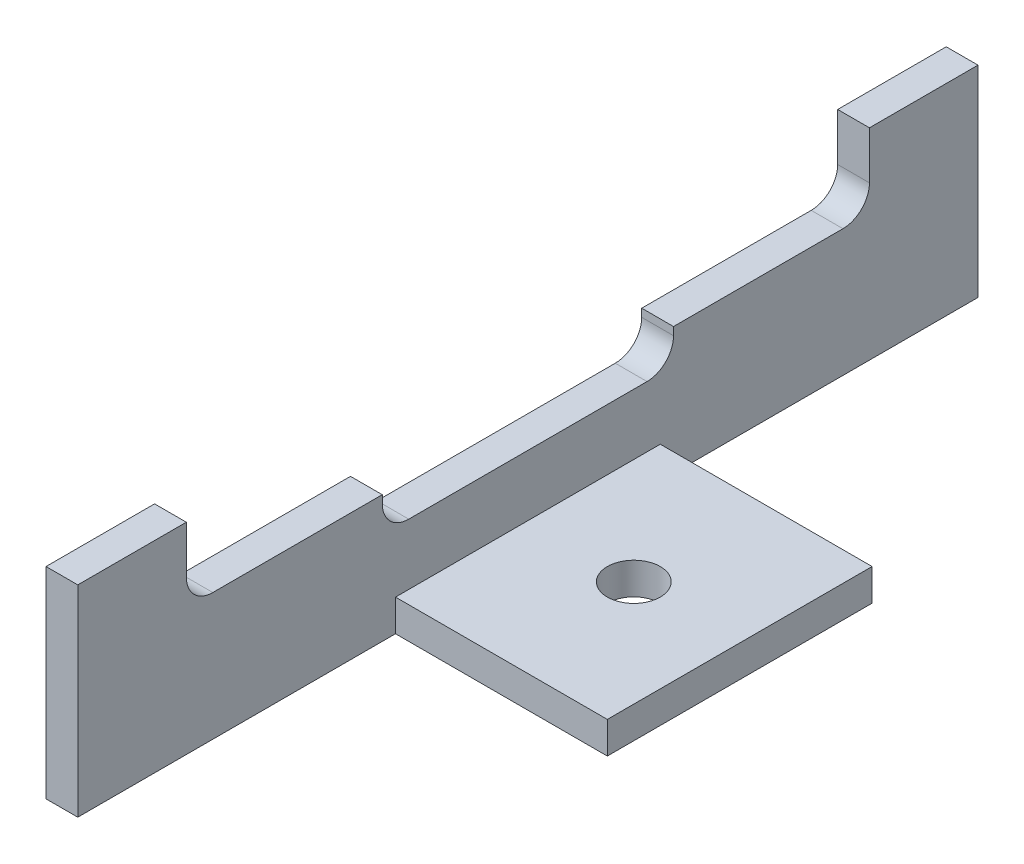
SolidWorks part; units mm, degrees
ref_plane "Alzado" through (0, 0, 0) normal (0, 0, 1) x (1, 0, 0)
ref_plane "Planta" through (0, 0, 0) normal (0, 1, 0) x (1, 0, 0)
ref_plane "Vista lateral" through (0, 0, 0) normal (1, 0, 0) x (0, 0, -1)
sketch "Croquis1" plane through (0, 0, 0) normal (0, 0, 1) x (1, 0, 0)
  line L0 (0, 0) -> (0, 50)
  line L1 (0, 0) -> (50, 0)
  line L2 (6, 6) -> (50, 6)
  line L3 (6, 6) -> (6, 50)
  line L4 (0, 50) -> (6, 50)
  line L5 (50, 6) -> (50, 0)
  dimension "D2" = 50
  dimension "D1" = 6
extrude "Saliente-Extruir1" add sketch "Croquis1" along normal blind 170
sketch "Croquis2" plane through (0, 0, 0) normal (-1, 0, 0) x (0, 0, 1)
  line L0 (170, 35) -> (0, 35) construction
  line L1 (170, 50) -> (170, 0) construction
  line L2 (0, 50) -> (0, 0) construction
  line L3 (170, 6) -> (0, 6) construction
  line L4 (170, 6) -> (0, 6) construction
  line L5 (85, 6) -> (85, 50) construction
  line L6 (170, 50) -> (0, 50) construction
  line L7 (112.5, 17.5) -> (112.5, 50)
  line L8 (112.5, 82.5) -> (57.5, 82.5) construction
  line L9 (112.5, 82.5) -> (112.5, 17.5) construction
  line L10 (112.5, 17.5) -> (57.5, 17.5)
  line L11 (57.5, 82.5) -> (57.5, 17.5) construction
  line L12 (112.5, 82.5) -> (57.5, 17.5) construction
  line L13 (112.5, 17.5) -> (57.5, 82.5) construction
  line L14 (57.5, 17.5) -> (57.5, 50)
  line L15 (57.5, 50) -> (112.5, 50)
  line L16 (149.5, 35) -> (149.5, 50)
  line L17 (130.5, 35) -> (130.5, 50)
  line L18 (130.5, 50) -> (149.5, 50)
  line L19 (39.5, 35) -> (39.5, 50)
  line L20 (20.5, 35) -> (20.5, 50)
  line L21 (39.5, 50) -> (20.5, 50)
  line L22 (170, 0) -> (0, 0) construction
  circle A0 centre (140, 35) radius 9.5 construction
  circle A1 centre (30, 35) radius 9.5 construction
  arc A2 (149.5, 35) -> (130.5, 35) centre (140, 35) cw
  arc A3 (39.5, 35) -> (20.5, 35) centre (30, 35) cw
  dimension "D2" = 19
  dimension "D1" = 35
  dimension "D3" = 55
  dimension "D4" = 55
  dimension "D5" = 17.5
  dimension "D6" = 55
  dimension "D7" = 20.5
  dimension "D8" = 20.5
extrude "Cortar-Extruir1" cut sketch "Croquis2" against normal up to surface (6 mm away) up to face at (6, 28, 85)
sketch "Croquis3" plane through (0, 0, 0) normal (0, -1, 0) x (1, 0, 0)
  line L0 (0, 85) -> (50, 85) construction
  line L1 (0, 170) -> (0, 0) construction
  line L2 (50, 170) -> (50, 0) construction
  line L3 (6, 170) -> (6, 0) construction
  line L4 (50, 0) -> (6, 0)
  line L5 (50, 0) -> (50, 60)
  line L6 (50, 60) -> (6, 60)
  line L7 (6, 0) -> (6, 60)
  line L8 (6, 170) -> (6, 0) construction
  line L9 (50, 110) -> (6, 110)
  line L10 (6, 170) -> (6, 110)
  line L11 (50, 170) -> (6, 170)
  line L12 (50, 170) -> (50, 110)
  line M5 (0, 0) -> (50, 0)
  line M6 (50, 0) -> (50, 170)
  line M7 (50, 170) -> (0, 170)
  dimension "D1" = 60
extrude "Cortar-Extruir2" cut sketch "Croquis3" against normal up to surface (6 mm away) contours L10 L9 M7 M6 | L7 L6 M5 M6 region at (28, 0, 140) region at (28, 0, 30) up to face at (28, 6, 85)
sketch "Croquis4" plane through (0, 0, 0) normal (0, -1, 0) x (1, 0, 0)
  line L0 (46, 60) -> (46, 110)
  line L1 (50, 60) -> (6, 60) construction
  line L2 (50, 110) -> (6, 110) construction
  line L3 (46, 110) -> (50, 110)
  line L4 (50, 110) -> (50, 60)
  line L5 (50, 60) -> (46, 60)
  dimension "D1" = 4
extrude "Cortar-Extruir3" cut sketch "Croquis4" against normal blind 10
sketch "Croquis5" plane through (0, 0, 0) normal (-1, 0, 0) x (0, 0, 1)
  line L0 (170, 38) -> (0, 38) construction
  line L1 (170, 50) -> (170, 0) construction
  line L2 (0, 50) -> (0, 0) construction
  line L3 (170, 50) -> (149.5, 50) construction
  line L4 (170, 38) -> (149.5, 38)
  line L5 (149.5, 38) -> (149.5, 50)
  line L6 (149.5, 50) -> (170, 50)
  line L7 (170, 50) -> (170, 38)
  line L8 (149.5, 35) -> (149.5, 50) construction
  line L9 (112.5, 50) -> (112.5, 38)
  line L10 (112.5, 17.5) -> (112.5, 50) construction
  line L11 (112.5, 38) -> (130.5, 38)
  line L12 (130.5, 50) -> (130.5, 35) construction
  line L13 (130.5, 38) -> (130.5, 50)
  line L14 (130.5, 50) -> (112.5, 50)
  line L15 (85, 17.5) -> (85, 38) construction
  line L16 (57.5, 17.5) -> (112.5, 17.5) construction
  line L17 (39.5, 38) -> (39.5, 50)
  line L18 (57.5, 38) -> (39.5, 38)
  line L19 (57.5, 50) -> (57.5, 38)
  line L20 (39.5, 50) -> (57.5, 50)
  line L21 (20.5, 50) -> (0, 50)
  line L22 (20.5, 38) -> (20.5, 50)
  line L23 (0, 38) -> (20.5, 38)
  line L24 (0, 50) -> (0, 38)
  dimension "D1" = 12
extrude "Cortar-Extruir4" cut sketch "Croquis5" against normal up to surface (6 mm away) up to face at (6, 28.4, 85)
sketch "Croquis6" plane through (0, 0, 0) normal (-1, 0, 0) x (0, 0, 1)
  line L0 (149.5, 38) -> (149.5, 24)
  line L1 (149.5, 24) -> (20.5, 24)
  line L2 (20.5, 24) -> (20.5, 38)
  line L3 (170, 0) -> (0, 0) construction
  line L4 (149.5, 38) -> (20.5, 38)
  dimension "D1" = 24
extrude "Cortar-Extruir5" cut sketch "Croquis6" against normal up to surface (6 mm away) up to face at (6, 23.6, 85)
fillet "Redondeo1" radius 5 2 edges at (3, 24, 149.5) (3, 24, 20.5)
fillet "Redondeo2" radius 5 2 edges at (3, 17.5, 57.5) (3, 17.5, 112.5)
sketch "Croquis7" plane through (0, 0, 0) normal (0, -1, 0) x (1, 0, 0)
  circle A0 centre (26, 85) radius 5 construction
  circle A1 centre (26, 85) radius 5
extrude "Cortar-Extruir6" cut sketch "Croquis7" against normal up to surface (6 mm away) up to face at (26, 6, 85)
